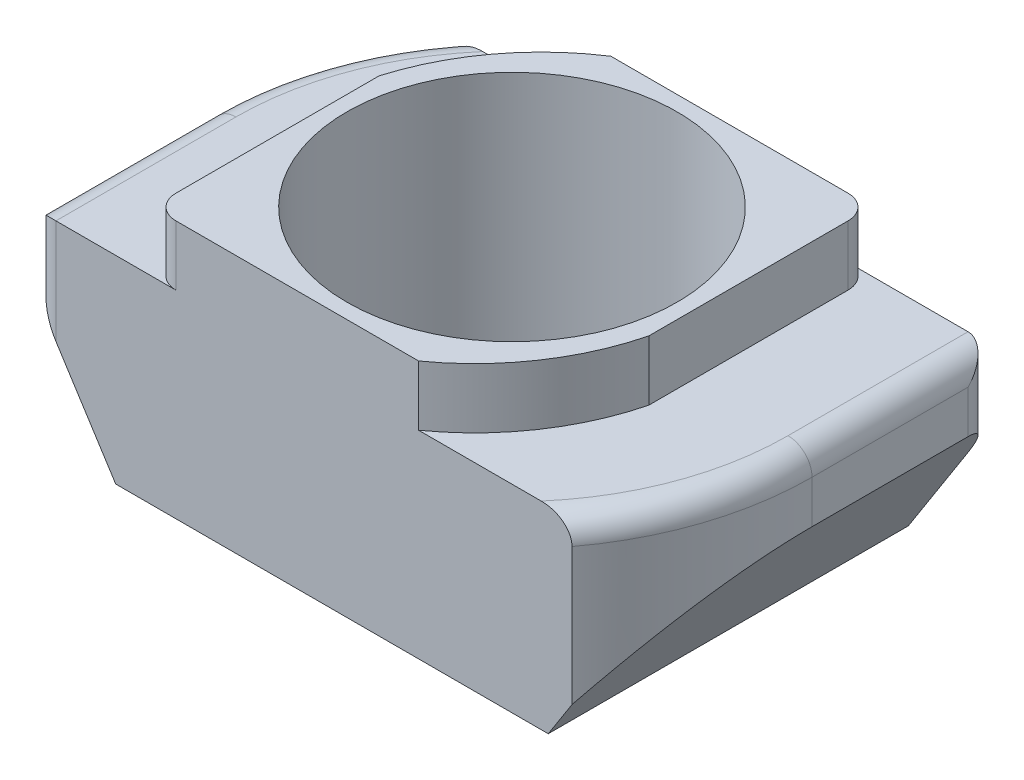
SolidWorks part; units mm, degrees
ref_plane "Front Plane" through (0, 0, 0) normal (0, 0, 1) x (1, 0, 0)
ref_plane "Top Plane" through (0, 0, 0) normal (0, 1, 0) x (1, 0, 0)
ref_plane "Right Plane" through (0, 0, 0) normal (1, 0, 0) x (0, 0, -1)
sketch "Sketch1" plane through (0, 0, 0) normal (0, 1, 0) x (1, 0, 0)
  line L1 (-5, -3) -> (4, -3)
  line L2 (-5, -3) -> (-5, 0)
  line L3 (-4, 3) -> (5, 3)
  line L4 (5, 0) -> (5, 3)
  line L5 (-5, -3) -> (5, 3) construction
  arc A0 (-4, 3) -> (-5, 0) centre (0, 0) ccw
  arc A1 (4, -3) -> (5, 0) centre (0, 0) ccw
  point P0 (0, 0)
  point P4 (0, 0)
  point P10 (0, 0)
  point P11 (4.9176, 3.7848)
  point P12 (-4, 3)
  point P13 (-4, 3)
  point P16 (0, 0)
  dimension "D4" = 5
  dimension "D1" = 10
  dimension "D2" = 6
  dimension "D3" = 2
extrude "Boss-Extrude1" add sketch "Sketch1" along normal blind 3.3
sketch "Sketch3" plane through (0, 3.3, 0) normal (0, 1, 0) x (1, 0, 0)
  line L0 (5, 3) -> (-4, 3) construction
  line L1 (-3, -3) -> (1.4435, -3)
  line L2 (-3, -3) -> (-3, 0.7854)
  line L3 (-1.3524, 3) -> (3, 3)
  line L4 (3, -0.7205) -> (3, 3)
  line L5 (-3, -3) -> (3, 3) construction
  line L6 (-2.1806, 2.2786) -> (2.1991, -2.2979) construction
  line L7 (-5, -3) -> (4, -3) construction
  arc A0 (-3, 0.7854) -> (-1.3524, 3) centre (0.836, -0.3483) cw
  arc A1 (3, -0.7205) -> (1.4435, -3) centre (-0.8788, 0.2569) cw
  point P0 (0, 0)
  point P15 (-0.0153, -0.0283)
  dimension "D2" = 4
  dimension "D1" = 6
  dimension "D3" = 2
extrude "Boss-Extrude2" add sketch "Sketch3" along normal blind 1
sketch "Sketch4" plane through (0, 4.3, 0) normal (0, 1, 0) x (1, 0, 0)
  circle A0 centre (0, 0) radius 2.75
  dimension "D1" = 5.5
extrude "Cut-Extrude1" cut sketch "Sketch4" against normal through all
sketch "Sketch5" plane through (0, 0, 3) normal (0, 0, 1) x (1, 0, 0)
  line L0 (4, 0) -> (5, 0) construction
  line L1 (5, 0) -> (5, 3.3) construction
  line L3 (-5, 0) -> (4, 0) construction
  line L9 (-5, 3.3) -> (-5, 0) construction
  line L10 (4, 0) -> (5, 0)
  line L11 (5, 0) -> (5, 2.186)
  line L13 (-5, 0) -> (-3.6042, 0)
  line L19 (-5, 2.186) -> (-5, 0)
  line L20 (-5, 2.186) -> (-3.6042, 0)
  line L21 (3.6042, 0) -> (4, 0)
  line L22 (5, 2.186) -> (3.6042, 0)
extrude "Cut-Extrude2" cut sketch "Sketch5" against normal through all
fillet "Fillet1" radius 0.4 8 edges at (5, 2.743, -3) (-5, 2.743, 3) (3, 3.8, -3) (-3, 3.8, 3) (4.7434, 3.3, 1.5811) (-4.7434, 3.3, -1.5811) (5, 3.3, -1.5) (-5, 3.3, 1.5)
